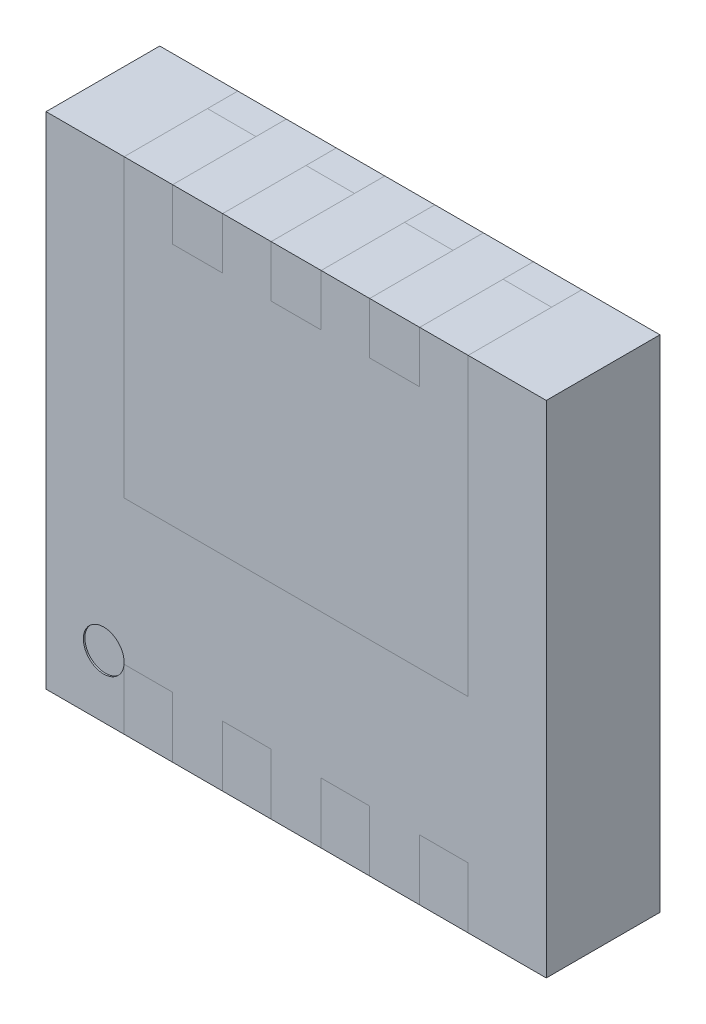
SolidWorks part; units mm, degrees
ref_plane "Front Plane" through (0, 0, 0) normal (0, 0, 1) x (1, 0, 0)
ref_plane "Top Plane" through (0, 0, 0) normal (0, 1, 0) x (1, 0, 0)
ref_plane "Right Plane" through (0, 0, 0) normal (1, 0, 0) x (0, 0, -1)
sketch "Sketch1" plane through (0, 0, 0) normal (0, 0, 1) x (1, 0, 0)
  line L0 (-0.975, -1.25) -> (-0.975, -1.65) construction
  line L1 (-1.65, -1.65) -> (1.65, -1.65)
  line L2 (-1.65, -1.65) -> (-1.65, 1.65)
  line L3 (-1.65, 1.65) -> (1.65, 1.65)
  line L4 (1.65, -1.65) -> (1.65, 1.65)
  line L5 (-1.65, -1.65) -> (1.65, 1.65) construction
  line L6 (-1.65, 1.65) -> (1.65, -1.65) construction
  line L7 (-1.135, -1.65) -> (-0.815, -1.65)
  line L8 (-1.135, -1.65) -> (-1.135, -1.25)
  line L9 (-1.135, -1.25) -> (-0.815, -1.25)
  line L10 (-0.815, -1.65) -> (-0.815, -1.25)
  line L11 (-0.485, -1.65) -> (-0.485, -1.25)
  line L12 (-0.485, -1.65) -> (-0.165, -1.65)
  line L13 (-0.165, -1.65) -> (-0.165, -1.25)
  line L14 (-0.485, -1.25) -> (-0.165, -1.25)
  line L15 (-0.325, -1.25) -> (-0.325, -1.65) construction
  line L16 (0.165, -1.65) -> (0.165, -1.25)
  line L17 (0.165, -1.65) -> (0.485, -1.65)
  line L18 (0.485, -1.65) -> (0.485, -1.25)
  line L19 (0.165, -1.25) -> (0.485, -1.25)
  line L20 (0.325, -1.25) -> (0.325, -1.65) construction
  line L21 (0.815, -1.65) -> (0.815, -1.25)
  line L22 (0.815, -1.65) -> (1.135, -1.65)
  line L23 (1.135, -1.65) -> (1.135, -1.25)
  line L24 (0.815, -1.25) -> (1.135, -1.25)
  line L25 (0.975, -1.25) -> (0.975, -1.65) construction
  line L26 (0, 2.1533) -> (0, -2.7533) construction
  line L28 (-1.135, 1.65) -> (1.135, 1.65)
  line L29 (-1.135, 1.65) -> (-1.135, -0.3)
  line L30 (-1.135, -0.3) -> (1.135, -0.3)
  line L31 (1.135, 1.65) -> (1.135, -0.3)
  line L32 (-0.815, 1.65) -> (-0.485, 1.65)
  line L33 (-0.815, 1.65) -> (-0.815, 1.31)
  line L34 (-0.815, 1.31) -> (-0.485, 1.31)
  line L35 (-0.485, 1.65) -> (-0.485, 1.31)
  line L43 (-0.65, 1.31) -> (-0.65, 1.65) construction
  line L44 (-0.165, 1.65) -> (-0.165, 1.31)
  line L45 (-0.165, 1.65) -> (0.165, 1.65)
  line L46 (0.165, 1.65) -> (0.165, 1.31)
  line L47 (-0.165, 1.31) -> (0.165, 1.31)
  line L48 (0.485, 1.65) -> (0.485, 1.31)
  line L49 (0.485, 1.65) -> (0.815, 1.65)
  line L50 (0.815, 1.65) -> (0.815, 1.31)
  line L51 (0.485, 1.31) -> (0.815, 1.31)
  line L52 (0, 1.65) -> (0, 1.31) construction
  line L53 (-1.135, 0.675) -> (0, 0.675) construction
  point P0 (0, 0)
  point P36 (0, -0.3)
  point P55 (0, 0)
  dimension "D1" = 3.3
  dimension "D2" = 3.3
  dimension "D3" = 0.32
  dimension "D4" = 0.4
  dimension "D5" = 4
  dimension "D6" = 0.325
  dimension "D7" = 1.95
  dimension "D8" = 1.95
  dimension "D9" = 2.27
  dimension "D10" = 0.34
  dimension "D11" = 0.33
  dimension "D12" = 0.32
  dimension "D13" = 3
  dimension "D14" = 0.32
extrude "Boss-Extrude1" add sketch "Sketch1" along normal blind 0.2 contours L51 L48 L3 L46 L47 L44 L35 L34 L33 L29 L30 L31 L50 | L1 L10 L9 L8 | L14 L11 L1 L13 | L19 L16 L1 L18 | L24 L21 L1 L23 region at (-0.975, -1.45, 0) region at (0, 0.6087, 0) region at (-0.325, -1.45, 0) region at (0.325, -1.45, 0) region at (0.975, -1.45, 0)
extrude "Boss-Extrude4" add sketch "Sketch1<5>" along normal blind 0.75 separate body contours L3 L31 L30 L29 L2 L1 L8 L9 L10 L11 L14 L13 L16 L19 L18 L21 L24 L23 L4 | L48 L51 L50 L28 | L35 L28 L33 L34 | L44 L47 L46 L45 region at (0, -0.3773, 0) region at (-0.65, 1.48, 0) region at (0.65, 1.48, 0)
sketch "Sketch1<5>" plane through (0, 0, 0) normal (0, 0, 1) x (1, 0, 0) same geometry as "Sketch1"
extrude "Boss-Extrude7" add sketch "Sketch1<7>" along normal blind 0.55 from offset 0.2 separate body contours L51 L48 L3 L46 L47 L44 L35 L34 L33 L29 L30 L31 L50 | L1 L10 L9 L8 | L14 L11 L1 L13 | L19 L16 L1 L18 | L24 L21 L1 L23 region at (-0.975, -1.45, 0) region at (0, 0.6087, 0) region at (-0.325, -1.45, 0) region at (0.325, -1.45, 0) region at (0.975, -1.45, 0)
sketch "Sketch1<7>" plane through (0, 0, 0) normal (0, 0, 1) x (1, 0, 0) same geometry as "Sketch1"
sketch "Sketch3" plane through (0, 0, 0.75) normal (0, 0, 1) x (1, 0, 0)
  circle A0 centre (-1.2695, -1.2388) radius 0.1345
extrude "Cut-Extrude1" cut sketch "Sketch3" against normal blind 0.01
